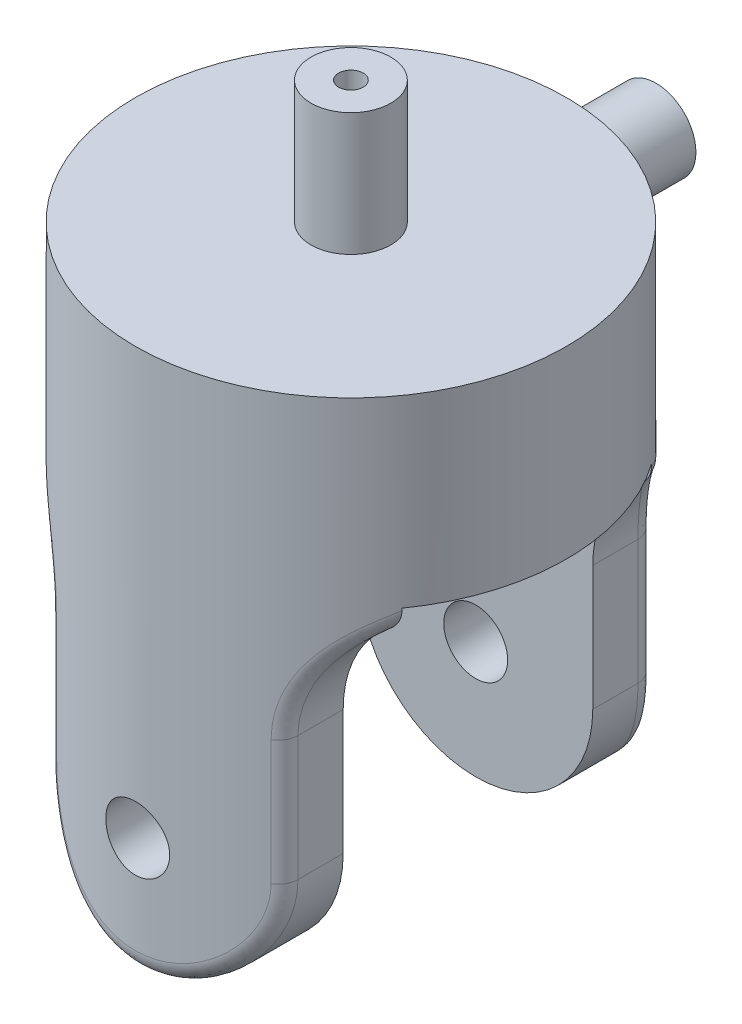
SolidWorks part; units mm, degrees
other "Markup1"
sketch "Sketch11" plane through (-17.55, 15, -20.84) normal (-0.5556, 0.8283, -0.0722) x (-0.0445, 0.0571, 0.9974)
ref_plane "Front Plane" through (0, 0, 0) normal (0, 0, 1) x (1, 0, 0)
ref_plane "Top Plane" through (0, 0, 0) normal (0, 1, 0) x (1, 0, 0)
ref_plane "Right Plane" through (0, 0, 0) normal (1, 0, 0) x (0, 0, -1)
sketch "Sketch1" plane through (0, 0, 0) normal (0, 1, 0) x (1, 0, 0)
  circle A0 centre (0, 0) radius 17.55
  dimension "D1" = 35.1
extrude "Boss-Extrude1" add sketch "Sketch1" along normal blind 15
ref_plane "Plane1" through (0, 0, 10.16) normal (0, 0, 1) x (1, 0, 0)
sketch "Sketch2" plane through (0, 0, 10.16) normal (0, 0, 1) x (1, 0, 0)
  line L0 (-9.53, -19.68) -> (-9.53, 0)
  line L1 (-17.55, 0) -> (17.55, 0) construction
  line L2 (-9.53, 0) -> (9.53, 0)
  line L3 (9.53, 0) -> (9.53, -19.68)
  circle A0 centre (0, -19.68) radius 2.6
  arc A1 (-9.53, -19.68) -> (9.53, -19.68) centre (0, -19.68) ccw
  dimension "D1" = 5.2
  dimension "D2" = 19.06
  dimension "D3" = 19.68
extrude "Boss-Extrude2" add sketch "Sketch2" along normal up to surface (7.1963 mm away)
mirror "Mirror1" about plane through (0, 0, 0) normal (0, 0, 1) of "Boss-Extrude2"
fillet "Fillet1" radius 9.53 4 edges at (-9.53, 0, -12.4485) (-9.53, 0, 12.4485) (9.53, 0, -12.4485) (9.53, 0, 12.4485)
fillet "Fillet2" radius 1.6 10 edges at (-0.4715, -29.1983, -17.5437) (-9.53, -14.605, -14.7371) (9.53, -14.605, -14.7371) (9.53, -14.605, 14.7371) (-10.9659, -4.4994, -13.7022) (-10.7842, -4.8044, 13.8457) (10.7842, -4.8044, -13.8457) (10.9659, -4.4994, 13.7022) (-0.4715, -29.1983, 17.5437) (-9.53, -14.605, 14.7371)
sketch "Sketch6" plane through (0, 0, 10.16) normal (0, 0, 1) x (1, 0, 0)
  circle A1 centre (0, 9.1156) radius 3.25
  dimension "D2" = 6.5
extrude "Boss-Extrude3" add sketch "Sketch6" against normal blind 35
sketch "Sketch8" plane through (0, 0, -24.84) normal (0, 0, -1) x (-1, 0, 0)
  circle A0 centre (0, 9.1156) radius 1
  dimension "D1" = 2
sketch "Sketch9" plane through (0, 15, 0) normal (0, 1, 0) x (1, 0, 0)
  circle A0 centre (0, 0) radius 1
  dimension "D1" = 2
extrude "Cut-Extrude5" cut sketch "Sketch8" against normal blind 20.8444
extrude "Cut-Extrude6" cut sketch "Sketch9" against normal blind 6
sketch "Sketch24" plane through (0, 15, 0) normal (0, 1, 0) x (1, 0, 0)
  circle A0 centre (0, 0) radius 3.25
  dimension "D1" = 6.5
extrude "Boss-Extrude6" add sketch "Sketch24" along normal blind 10
sketch "Sketch26" plane through (0, 25, 0) normal (0, 1, 0) x (1, 0, 0)
  circle A0 centre (0, 0) radius 1
  dimension "D1" = 2
extrude "Cut-Extrude7" cut sketch "Sketch26" against normal up to surface (10 mm away) contours A0 up to face at (0, 15, 3.25)
